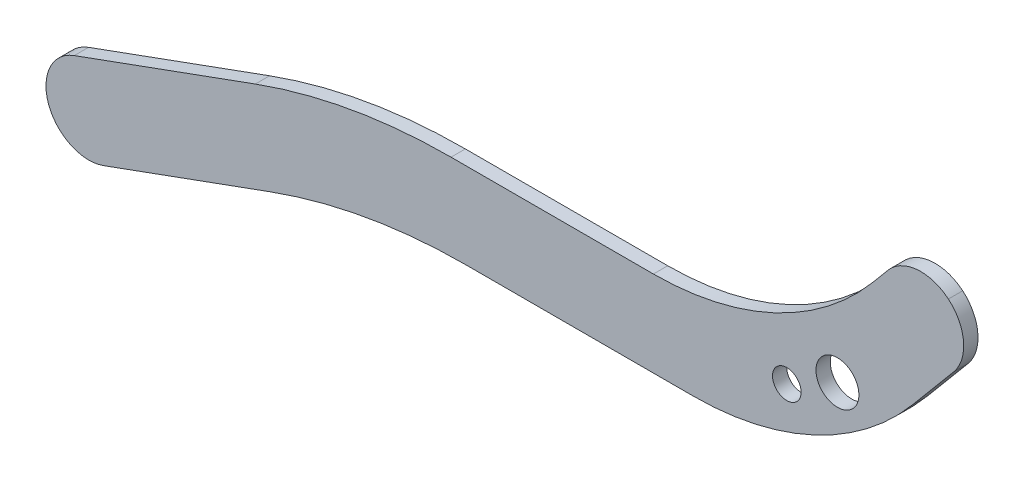
SolidWorks part; units mm, degrees
ref_plane "前视基准面" through (0, 0, 0) normal (0, 0, 1) x (1, 0, 0)
ref_plane "上视基准面" through (0, 0, 0) normal (0, 1, 0) x (1, 0, 0)
ref_plane "右视基准面" through (0, 0, 0) normal (1, 0, 0) x (0, 0, -1)
other "Configuration Table"
sketch "草图1" plane through (0, 0, 0) normal (0, 0, 1) x (1, 0, 0)
  line L0 (-21.5192, -15.6178) -> (-113.5892, -54.6449)
  line L1 (55.0061, 52.4521) -> (12.9053, 31.2865)
  line L2 (12.9053, 31.2865) -> (-29.3246, 2.7962)
  line L3 (-29.3246, 2.7962) -> (-121.3946, -36.2309)
  line L4 (-113.5892, -54.6449) -> (-21.5192, -15.6178)
  line L5 (-21.5192, -15.6178) -> (24.0651, -10.415)
  line L6 (24.0651, -10.415) -> (75.6243, 11.4401)
  circle A0 centre (50.8892, 38.9924) radius 1.6
  circle A1 centre (50.9962, 25.9816) radius 1.6
  circle A2 centre (60.2719, 16.8573) radius 1.6
  circle A3 centre (-117.4919, -45.4379) radius 2.5
  circle A4 centre (66.6481, 32.6162) radius 2.5
  circle A5 centre (-103.6814, -39.5838) radius 2.5
  circle A6 centre (41.3687, 15.3839) radius 1.5
  circle A7 centre (36.6855, 26.4323) radius 1.5
  circle A8 centre (27.5582, 9.5298) radius 1.5
  circle A9 centre (22.875, 20.5782) radius 1.5
  circle A10 centre (13.7477, 3.6758) radius 1.5
  circle A11 centre (9.0645, 14.7242) radius 1.5
  circle A12 centre (-0.0628, -2.1783) radius 1.5
  circle A13 centre (-4.746, 8.8701) radius 1.5
  circle A14 centre (-13.8733, -8.0323) radius 1.5
  circle A15 centre (-18.5565, 3.0161) radius 1.5
  circle A16 centre (-27.6838, -13.8864) radius 1.5
  circle A17 centre (-32.367, -2.838) radius 1.5
  circle A18 centre (-41.4943, -19.7405) radius 1.5
  circle A19 centre (-46.1775, -8.692) radius 1.5
  circle A20 centre (-55.3048, -25.5945) radius 1.5
  circle A21 centre (-59.988, -14.5461) radius 1.5
  circle A22 centre (-69.1153, -31.4486) radius 1.5
  circle A23 centre (-73.7985, -20.4002) radius 1.5
  circle A24 centre (-82.9258, -37.3026) radius 1.5
  circle A25 centre (-87.609, -26.2542) radius 1.5
  circle A26 centre (82.3, 39.2508) radius 1.6
  circle A27 centre (82.4071, 26.24) radius 1.6
  circle A28 centre (73.0243, 48.3752) radius 1.6
  circle A29 centre (96.4227, 28.9453) radius 6.5
  arc A30 (-121.3946, -36.2309) -> (-113.5892, -54.6449) centre (-117.4919, -45.4379) ccw
  arc A31 (79.8323, 51.4624) -> (94.2394, 44.5072) centre (108.4934, 92.4324) ccw
  arc A32 (79.8323, 51.4624) -> (55.0061, 52.4521) centre (66.6481, 32.6162) ccw
  arc A33 (-121.3946, -36.2309) -> (-113.5892, -54.6449) centre (-117.4919, -45.4379) ccw
  parabola Q0 (75.6243, 11.4401) -> (94.2394, 44.5072) focus (124.991, 27.1237) apex (126.7522, 27.0114)
sketch "草图2" plane through (0, 0, 0) normal (0, 0, 1) x (1, 0, 0)
  line L0 (-150, 0) -> (0, 0) construction
  line L1 (-150, 15) -> (0, 15)
  line L2 (-150, -15) -> (0, -15)
  line L3 (0, 0) -> (0, 233.0744) construction
  line L4 (0, 0) -> (338.834, 0) construction
  line L5 (-152.6449, 15) -> (-150, 15)
  line L6 (0, 15) -> (44.9951, 68.6231)
  line L7 (-150, 0) -> (-243.9693, -34.202) construction
  line L8 (13.9892, -15) -> (67.9765, 49.3395)
  line L9 (-144.8697, -14.0954) -> (-238.839, -48.2974)
  line L10 (44.9951, 68.6231) -> (67.9765, 49.3395)
  line L11 (-155.1303, 14.0954) -> (-249.0996, -20.1066)
  line L13 (-155.1303, 14.0954) -> (-152.6449, 15)
  line L14 (0, -15) -> (13.9892, -15)
  arc A0 (-150, 15) -> (-150, -15) centre (-150, 0) ccw
  arc A1 (0, -15) -> (0, 15) centre (0, 0) ccw
  arc A4 (-144.8697, -14.0954) -> (-155.1303, 14.0954) centre (-150, 0) ccw
  arc A5 (-249.0996, -20.1066) -> (-238.839, -48.2974) centre (-243.9693, -34.202) ccw
  circle A7 centre (17.6993, 14.3131) radius 7.5
  circle A8 centre (0, 5) radius 5
  point P2 (-75, 0)
  point P11 (-196.9846, -17.101)
  point P27 (0, 5)
  point P31 (0, 4.8165)
  point P32 (0.1181, 5.0974)
  dimension "D2" = 15
  dimension "D12" = 15
  dimension "D8" = 20
  dimension "D13" = 15
  dimension "D9" = 20
  dimension "D11" = 10
  dimension "D3" = 150
  dimension "D4" = 130
  dimension "D5" = 100
  dimension "D6" = 70
  dimension "D7" = 30
  dimension "D10" = 160
  dimension "D14" = 14
extrude "凸台-拉伸1" add sketch "草图2" along normal blind 5 contours A0 L5 L13 | L11 A5 L9 L2 A0 | L9 A4 A0 L2 | A4 L9 L2 A1 L1 | A1 L14 L8 L10 L6 region at (-152.6128, 14.8181, 0) region at (-149.9985, -0.0085, 0) region at (-64.3344, -0.0875, 0) region at (34.964, 32.0067, 0) region at (-208.0633, -21.1312, 0)
fillet "圆角1" radius 200 2 edges at (-152.6449, 15, 2.5) (-147.3551, -15, 2.5)
fillet "圆角2" radius 100 2 edges at (0, 15, 2.5) (13.9892, -15, 2.5)
fillet "圆角3" radius 15 2 edges at (44.9951, 68.6231, 2.5) (67.9765, 49.3395, 2.5)
